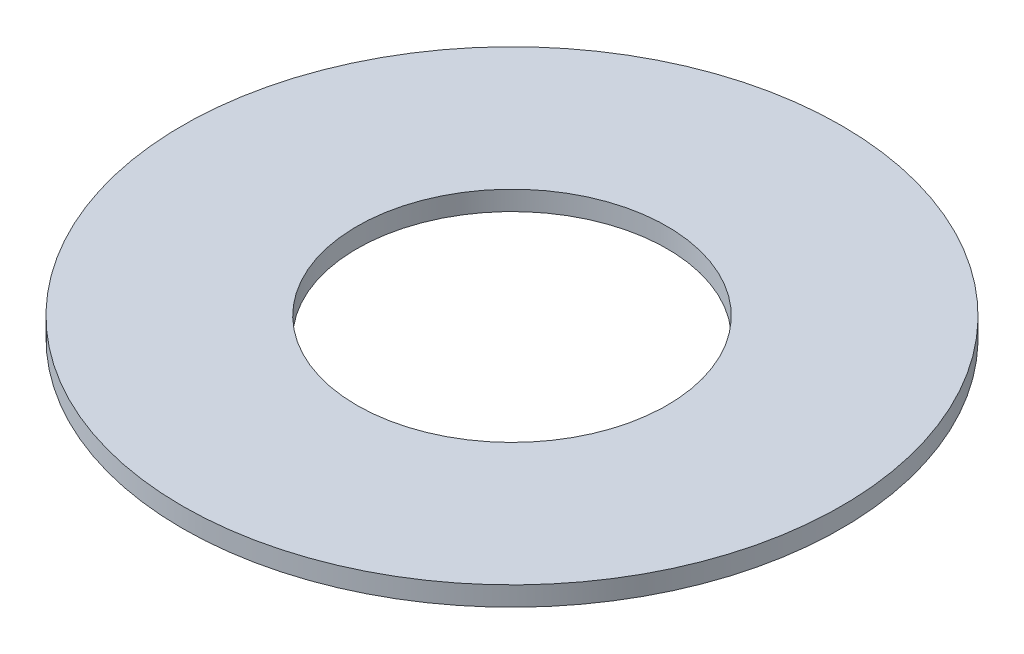
SolidWorks part; units mm, degrees
ref_plane "Front Plane" through (0, 0, 0) normal (0, 0, 1) x (1, 0, 0)
ref_plane "Top Plane" through (0, 0, 0) normal (0, 1, 0) x (1, 0, 0)
ref_plane "Right Plane" through (0, 0, 0) normal (1, 0, 0) x (0, 0, -1)
sketch "Sketch1" plane through (0, 0, 0) normal (0, 1, 0) x (1, 0, 0)
  circle A0 centre (0, 0) radius 85
  dimension "FLANGE_OD" = 170
extrude "Boss-Extrude1" add sketch "Sketch1" along normal blind 5
sketch "Sketch2" plane through (0, 0, 0) normal (0, 1, 0) x (1, 0, 0)
  circle A0 centre (0, 0) radius 40
  dimension "BORE_D" = 80
extrude "Cut-Extrude1" cut sketch "Sketch2" along normal through all
sketch "Sketch3" plane through (0, 5, 0) normal (0, 1, 0) x (1, 0, 0)
  circle A0 centre (0, 0) radius 29.5858 construction
  circle A1 centre (-29.5858, 0) radius 1.5697
  dimension "BOLT_D" = 3.1395
  dimension "BOLT_PCD" = 59.1715
extrude "Cut-Extrude2" cut sketch "Sketch3" against normal blind 4.33 rebuild error yes
pattern_circular "CirPattern1" count 8 over 360 rebuild error yes
